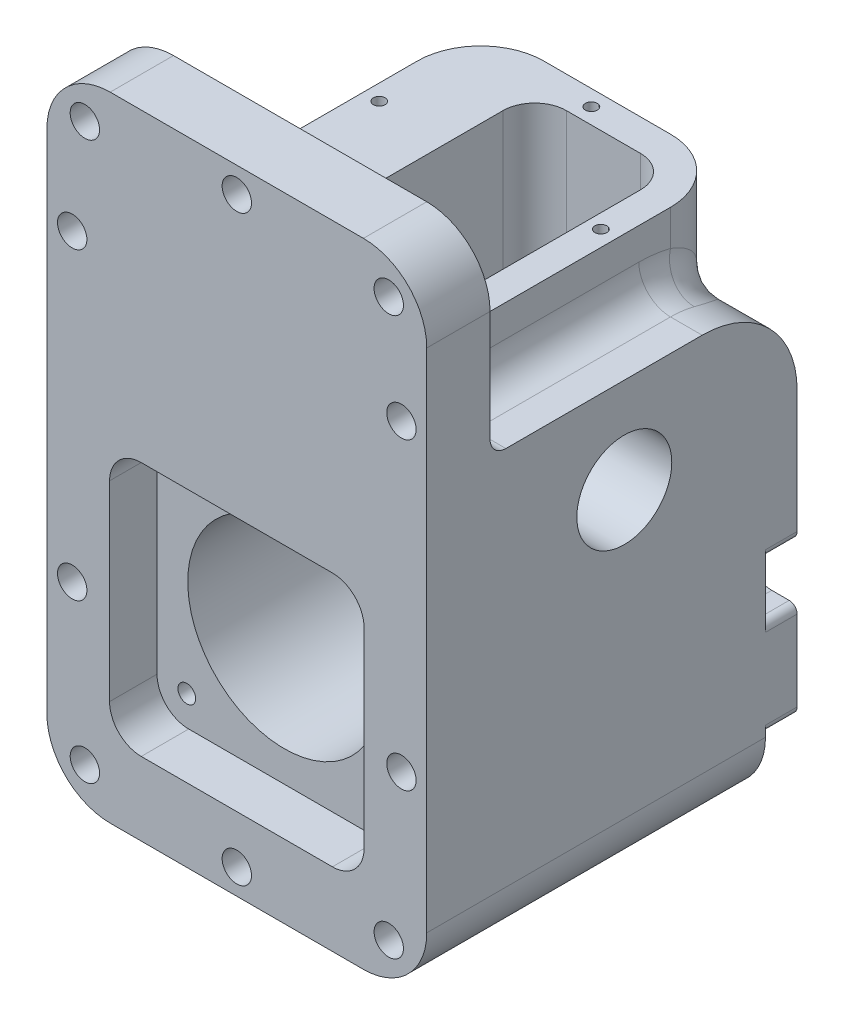
SolidWorks part; units mm, degrees
ref_plane "Front Plane" through (0, 0, 0) normal (0, 0, 1) x (1, 0, 0)
ref_plane "Top Plane" through (0, 0, 0) normal (0, 1, 0) x (1, 0, 0)
ref_plane "Right Plane" through (0, 0, 0) normal (1, 0, 0) x (0, 0, -1)
sketch "Sketch2" plane through (0, 0, 0) normal (0, 0, 1) x (1, 0, 0)
  line L1 (-19.05, -31.75) -> (19.05, -31.75)
  line L2 (-19.05, -31.75) -> (-19.05, 31.75)
  line L3 (-19.05, 31.75) -> (19.05, 31.75)
  line L4 (19.05, -31.75) -> (19.05, 31.75)
  line L5 (-19.05, -31.75) -> (19.05, 31.75) construction
  line L6 (-19.05, 31.75) -> (19.05, -31.75) construction
  point P0 (0, 0)
  dimension "D1" = 63.5
  dimension "D2" = 38.1
extrude "Boss-Extrude1" add sketch "Sketch2" along normal blind 6.35
fillet "Fillet1" radius 6.35 4 edges at (-19.05, -31.75, 3.175) (19.05, -31.75, 3.175) (-19.05, 31.75, 3.175) (19.05, 31.75, 3.175)
hole_wizard "#4 Clearance Hole1" positions "Sketch4" profile "Sketch5" hole size "#4" standard "Ansi Inch" end condition through all
sketch "Sketch4" plane through (0, 0, 6.35) normal (0, 0, 1) x (1, 0, 0)
  line L0 (12.7, 31.75) -> (-12.7, 31.75) construction
  line L1 (-12.7, -31.75) -> (12.7, -31.75) construction
  line L2 (-17.1901, -29.8901) -> (0, -12.7) construction
  line L3 (0, -12.7) -> (17.1901, -29.8901) construction
  line L5 (-17.1901, 29.8901) -> (0, 12.7) construction
  line L6 (0, 12.7) -> (17.1901, 29.8901) construction
  line L8 (-19.05, 25.4) -> (-19.05, -25.4) construction
  line L9 (19.05, -25.4) -> (19.05, 25.4) construction
  arc A0 (-19.05, -25.4) -> (-12.7, -31.75) centre (-12.7, -25.4) ccw construction
  arc A1 (12.7, -31.75) -> (19.05, -25.4) centre (12.7, -25.4) ccw construction
  arc A2 (-12.7, 31.75) -> (-19.05, 25.4) centre (-12.7, 25.4) ccw construction
  arc A3 (19.05, 25.4) -> (12.7, 31.75) centre (12.7, 25.4) ccw construction
  point P0 (0, 29.21)
  point P1 (-15.24, 27.94)
  point P3 (15.24, 27.94)
  point P5 (-15.24, -27.94)
  point P7 (15.24, -27.94)
  point P9 (-16.51, 17.78)
  point P11 (-16.51, -12.7)
  point P13 (16.51, 17.78)
  point P15 (16.51, -12.7)
  point P17 (0, -29.21)
  dimension "D1" = 2.54
  dimension "D2" = 2.54
  dimension "D3" = 15.24
  dimension "D4" = 15.24
  dimension "D5" = 2.54
  dimension "D6" = 2.54
  dimension "D7" = 17.78
  dimension "D8" = 30.48
  dimension "D9" = 30.48
  dimension "D10" = 17.78
sketch "Sketch5" plane through (0, 29.21, 6.35) normal (1, 0, 0) x (0, -1, 0)
  line L0 (0, 0) -> (0, 6.35)
  line L1 (0, 6.35) -> (1.4732, 6.35)
  line L2 (1.4732, 6.35) -> (1.4732, 0)
  line L5 (1.4732, 0) -> (0, 0)
  line L11 (0, -6.35) -> (0, 107.95) construction
  dimension "Thru Hole Dia." = 2.9464
  dimension "Thru Hole Depth" = 6.35
sketch "Sketch6" plane through (0, 0, 0) normal (0, 0, -1) x (-1, 0, 0)
  line L1 (-12.7, -25.4) -> (12.7, -25.4)
  line L2 (-12.7, -25.4) -> (-12.7, 25.4)
  line L3 (-12.7, 25.4) -> (12.7, 25.4)
  line L4 (12.7, -25.4) -> (12.7, 25.4)
  line L5 (-12.7, -25.4) -> (12.7, 25.4) construction
  line L6 (-12.7, 25.4) -> (12.7, -25.4) construction
  point P0 (0, 0)
  dimension "D1" = 50.8
  dimension "D2" = 25.4
extrude "Boss-Extrude2" add sketch "Sketch6" along normal blind 35.56
sketch "Sketch7" plane through (0, 0, -35.56) normal (0, 0, -1) x (-1, 0, 0)
  line L0 (0, -25.4) -> (0, 25.4) construction
  line L1 (-12.7, -25.4) -> (12.7, -25.4) construction
  line L2 (12.7, 25.4) -> (-12.7, 25.4) construction
  line L3 (-12.7, 0) -> (12.7, 0) construction
  line L4 (-12.7, 25.4) -> (-12.7, -25.4) construction
  line L5 (12.7, -25.4) -> (12.7, 25.4) construction
  line L6 (-12.7, 3.175) -> (12.7, 3.175) construction
  line L7 (-12.7, 25.4) -> (-12.7, -25.4) construction
  line L8 (12.7, -25.4) -> (12.7, 25.4) construction
  circle A0 centre (0, -11.6332) radius 3.9688
  circle A1 centre (0, -11.6332) radius 11 construction
  dimension "D1" = 7.9375
  dimension "D4" = 22
  dimension "D2" = 3.175
  dimension "D3" = 14.8082
extrude "Cut-Extrude1" cut sketch "Sketch7" against normal through all
sketch "Sketch9" plane through (12.7, 0, 0) normal (1, 0, 0) x (0, 0, -1)
  line L0 (0, 0) -> (35.56, 0) construction
  line L1 (35.56, 25.4) -> (35.56, -25.4) construction
  line L2 (-6.35, -25.4) -> (-6.35, 25.4) construction
  circle A0 centre (13.462, 3.175) radius 4.7625
  dimension "D2" = 9.525
  dimension "D1" = 3.175
  dimension "D3" = 19.812
extrude "Cut-Extrude3" cut sketch "Sketch9" against normal through all
sketch "Sketch8" plane through (0, 0, 6.35) normal (0, 0, 1) x (1, 0, 0)
  circle A0 centre (0, -11.6332) radius 9.6837
  dimension "D1" = 19.3675
extrude "Cut-Extrude2" cut sketch "Sketch8" against normal offset from surface (38.735 mm away) 3.175 up to face at (-3.9688, -11.6332, -35.56)
sketch "Sketch11" plane through (0, 0, -32.385) normal (0, 0, 1) x (1, 0, 0)
  circle A0 centre (0, -11.6332) radius 9.6837
  circle A1 centre (0, -11.6332) radius 3.9688 construction
  circle A2 centre (0, -11.6332) radius 3.9688
  circle A3 centre (0, -11.6332) radius 9.6837 construction
extrude "Boss-Extrude3" add sketch "Sketch11" along normal offset from surface (7.9375 mm away) 11.1125 up to face at (-3.9688, -11.6332, -35.56)
sketch "Sketch10" plane through (0, 25.4, 0) normal (0, 1, 0) x (1, 0, 0)
  line L3 (0, 35.56) -> (0, 0) construction
  line L4 (-4.0957, 0) -> (9.6838, 0)
  line L5 (-4.0957, 0) -> (-4.0958, 27.6225)
  line L6 (-4.0958, 27.6225) -> (9.6837, 27.6225)
  line L7 (9.6838, 0) -> (9.6837, 27.6225)
  line L9 (-12.7, 0) -> (12.7, 0) construction
  line L10 (-12.7, 35.56) -> (12.7, 35.56) construction
  point P4 (0, 17.78)
  point P6 (2.794, 17.78)
  dimension "D1" = 13.7795
  dimension "D2" = 27.6225
  dimension "D3" = 4.0957
extrude "Cut-Extrude4" cut sketch "Sketch10" against normal blind 30.48
fillet "Fillet4" [suppressed] radius 3.175
fillet "Fillet5" radius 3.175 4 edges at (-4.0957, 11.2709, 0) (-4.0958, 10.16, -27.6225) (9.6838, 10.16, 0) (9.6837, 10.16, -27.6225)
sketch "Sketch13" plane through (0, 0, 6.35) normal (0, 0, 1) x (1, 0, 0)
  line L0 (0, -1.9495) -> (9.6837, -1.9495)
  line L1 (9.6837, -11.6332) -> (9.6837, -1.9495)
  arc A0 (-4.0958, -2.8582) -> (7.1296, -5.08) centre (0, -11.6332) ccw construction
  arc A1 (9.6837, -11.6332) -> (0, -1.9495) centre (0, -11.6332) ccw
extrude "Cut-Extrude5" cut sketch "Sketch13" against normal up to surface (30.7975 mm away) up to face at (-1.4863, -10.0606, -24.4475)
fillet "Fillet6" radius 3.175 1 edges at (9.6838, -1.9495, 1.5875)
sketch "Sketch14" plane through (12.7, 0, 0) normal (1, 0, 0) x (0, 0, -1)
  line L0 (35.56, -25.4) -> (0, -25.4) construction
  line L1 (35.56, 25.4) -> (30.7975, 25.4)
  line L2 (35.56, 25.4) -> (35.56, -25.4)
  line L3 (35.56, -25.4) -> (30.7975, -25.4)
  line L4 (30.7975, 25.4) -> (30.7975, -25.4)
  dimension "D1" = 4.7625
extrude "Cut-Extrude6" cut sketch "Sketch14" against normal up to next
sketch "Sketch15" plane through (0, 0, -30.7975) normal (0, 0, -1) x (-1, 0, 0)
  line L0 (12.7, -25.4) -> (12.7, 25.4) construction
  line L1 (-12.7, 25.4) -> (12.7, 25.4)
  line L2 (-12.7, 25.4) -> (-12.7, 19.05)
  line L3 (-12.7, 19.05) -> (12.7, 19.05)
  line L4 (12.7, 25.4) -> (12.7, 19.05)
  dimension "D1" = 6.35
extrude "Cut-Extrude7" cut sketch "Sketch15" against normal up to surface (30.7975 mm away) up to face at (1.2417, 4.991, 0)
fillet "Fillet8" [suppressed] radius 6.35
hole_wizard "#0-80 Tapped Hole1" positions "Sketch21" profile "Sketch22" tap size "#0-80" standard "Ansi Inch"
sketch "Sketch21" plane through (0, 19.05, 0) normal (0, 1, 0) x (-1, 0, 0)
  line L3 (12.7, 0) -> (0.9207, 0) construction
  line L5 (12.7, 0) -> (12.7, -30.7975) construction
  line L6 (0, -30.7975) -> (0, -27.6225) construction
  line L7 (-12.7, -30.7975) -> (12.7, -30.7975) construction
  line L8 (-6.5087, -27.6225) -> (0.9208, -27.6225) construction
  line L10 (-12.7, 0) -> (-12.7, -30.7975) construction
  point P0 (-11.1125, -19.05)
  point P6 (11.1125, -19.05)
  point P10 (0, -29.21)
  point P14 (-11.1125, -6.35)
  point P16 (11.1125, -6.35)
  dimension "D1" = 6.35
  dimension "D2" = 12.7
  dimension "D3" = 1.5875
  dimension "D4" = 1.5875
  dimension "D5" = 1.5875
sketch "Sketch22" plane through (11.1125, 19.05, -19.05) normal (1, 0, 0) x (0, 0, 1)
  line L0 (0, 0) -> (0, 4.4219)
  line L1 (0, 4.4219) -> (0.5956, 4.064)
  line L2 (0.5956, 4.064) -> (0.5956, 0)
  line L5 (0.5956, 0) -> (0, 0)
  line L10 (0, 4.4219) -> (-0.5956, 4.064) construction
  line L11 (0, -6.35) -> (0, 107.95) construction
  dimension "Tap Drill Dia." = 1.1913
  dimension "Tap Drill Depth" = 4.064
  dimension "Drill Angle" = 118
cosmetic thread "Hole Thread1" parameters "D1"=3.048, "D2"=1.524
cosmetic thread "Hole Thread2" parameters "D1"=3.048, "D2"=1.524
cosmetic thread "Hole Thread3" parameters "D1"=3.048, "D2"=1.524
cosmetic thread "Hole Thread4" parameters "D1"=3.048, "D2"=1.524
cosmetic thread "Hole Thread5" parameters "D1"=3.048, "D2"=1.524
sketch "Sketch23" plane through (0, 0, 6.35) normal (0, 0, 1) x (1, 0, 0)
  line L1 (-12.7635, -24.3967) -> (12.7635, -24.3967)
  line L2 (-12.7635, -24.3967) -> (-12.7635, 1.1303)
  line L3 (-12.7635, 1.1303) -> (12.7635, 1.1303)
  line L4 (12.7635, -24.3967) -> (12.7635, 1.1303)
  line L5 (-12.7635, -24.3967) -> (12.7635, 1.1303) construction
  line L6 (-12.7635, 1.1303) -> (12.7635, -24.3967) construction
  point P0 (0, -11.6332)
  dimension "D1" = 25.527
  dimension "D2" = 25.527
extrude "Cut-Extrude11" cut sketch "Sketch23" against normal blind 4.7625
fillet "Fillet9" radius 3.175 4 edges at (12.7635, 1.1303, 3.9688) (12.7635, -24.3967, 3.9688) (-12.7635, 1.1303, 3.9688) (-12.7635, -24.3967, 3.9688)
sketch "Sketch24" plane through (0, 0, 1.5875) normal (0, 0, 1) x (1, 0, 0)
  line L1 (-9.779, -21.4122) -> (9.779, -21.4122) construction
  line L2 (-9.779, -21.4122) -> (-9.779, -1.8542) construction
  line L3 (-9.779, -1.8542) -> (9.779, -1.8542) construction
  line L4 (9.779, -21.4122) -> (9.779, -1.8542) construction
  line L5 (-9.779, -21.4122) -> (9.779, -1.8542) construction
  line L6 (-9.779, -1.8542) -> (9.779, -21.4122) construction
  point P0 (0, -11.6332)
  dimension "D1" = 19.558
  dimension "D2" = 19.558
hole_wizard "#2-56 Tapped Hole1" positions "Sketch26" profile "Sketch25" tap size "#2-56" standard "Ansi Inch"
sketch "Sketch26" plane through (0, 0, 1.5875) normal (0, 0, 1) x (1, 0, 0)
  point P0 (-9.779, -1.8542)
  point P4 (-9.779, -21.4122)
  point P7 (9.779, -21.4122)
sketch "Sketch25" plane through (-9.779, -1.8542, 1.5875) normal (1, 0, 0) x (0, -1, 0)
  line L0 (0, 0) -> (0, 6.1222)
  line L1 (0, 6.1222) -> (0.889, 5.588)
  line L2 (0.889, 5.588) -> (0.889, 0)
  line L5 (0.889, 0) -> (0, 0)
  line L10 (0, 6.1222) -> (-0.889, 5.588) construction
  line L11 (0, -6.35) -> (0, 107.95) construction
  dimension "Tap Drill Dia." = 1.778
  dimension "Tap Drill Depth" = 5.588
  dimension "Drill Angle" = 118
cosmetic thread "Hole Thread6" parameters "D1"=4.318, "D2"=2.1844
cosmetic thread "Hole Thread7" parameters "D1"=4.318, "D2"=2.1844
cosmetic thread "Hole Thread9" parameters "D1"=4.318, "D2"=2.1844
sketch "Sketch27" plane through (12.7, 0, 0) normal (1, 0, 0) x (0, 0, -1)
  line L0 (30.7975, 12.7) -> (0, 12.7)
  line L1 (0, -25.4) -> (0, 25.4) construction
  line L2 (30.7975, -6.35) -> (0, -6.35)
  line L3 (0, -6.35) -> (0, 12.7)
  line L4 (30.7975, 19.05) -> (30.7975, -25.4) construction
  line L5 (30.7975, 12.7) -> (30.7975, -6.35)
  circle A1 centre (13.462, 3.175) radius 4.7625 construction
  circle A2 centre (13.462, 3.175) radius 4.7625
  dimension "D1" = 19.05
  dimension "D2" = 9.525
extrude "Boss-Extrude4" add sketch "Sketch27" along normal blind 6.35
mirror "Mirror1" about plane through (0, 0, 0) normal (1, 0, 0) of "Boss-Extrude4"
ref_axis "Axis2" through (9.6837, 3.175, -13.462) along (1, 0, 0)
ref_plane "Plane1" through (0, 0, -13.462) normal (0, 0, -1) x (-1, 0, 0)
sketch "Sketch30" plane through (0, 0, 0) normal (0, 0, -1) x (-1, 0, 0)
  line L0 (-19.05, -25.4) -> (-19.05, -6.35) construction
  line L1 (-19.05, -25.4) -> (-19.05, -6.35)
  line L6 (19.05, -6.35) -> (12.7, -6.35)
  line L7 (19.05, -6.35) -> (12.7, -6.35)
  line L12 (12.7, -6.35) -> (12.7, -25.4)
  line L13 (12.7, -6.35) -> (12.7, -25.4)
  line L14 (12.7, -25.4) -> (-12.7, -25.4)
  line L15 (-19.05, -6.35) -> (-19.05, -25.4)
  line L16 (-12.7, -31.75) -> (12.7, -31.75)
  line L17 (19.05, -25.4) -> (19.05, -6.35)
  line L18 (12.7, -25.4) -> (-12.7, -25.4)
  line L19 (-12.7, -25.4) -> (-12.7, -6.35)
  line L20 (-12.7, -25.4) -> (-12.7, -6.35)
  line L21 (-12.7, -6.35) -> (-19.05, -6.35)
  line L22 (-12.7, -6.35) -> (-19.05, -6.35)
  line L23 (-19.05, -6.35) -> (-19.05, -25.4)
  line L24 (-12.7, -31.75) -> (12.7, -31.75)
  line L25 (19.05, -25.4) -> (19.05, -6.35)
  arc A2 (-19.05, -25.4) -> (-12.7, -31.75) centre (-12.7, -25.4) ccw
  arc A3 (12.7, -31.75) -> (19.05, -25.4) centre (12.7, -25.4) ccw
  arc A4 (-19.05, -25.4) -> (-12.7, -31.75) centre (-12.7, -25.4) ccw
  arc A5 (12.7, -31.75) -> (19.05, -25.4) centre (12.7, -25.4) ccw
  line M11 (19.05, -6.35) -> (12.7, -6.35)
  line M12 (12.7, -6.35) -> (12.7, -25.4)
  line M13 (12.7, -25.4) -> (-12.7, -25.4)
  line M14 (-12.7, -25.4) -> (-12.7, -6.35)
  line M15 (-12.7, -6.35) -> (-19.05, -6.35)
  line M16 (-19.05, -6.35) -> (-19.05, -25.4)
  arc M17 (-19.05, -25.4) -> (-12.7, -31.75) centre (-12.7, -25.4) ccw
  line M18 (-12.7, -31.75) -> (12.7, -31.75)
  arc M19 (12.7, -31.75) -> (19.05, -25.4) centre (12.7, -25.4) ccw
  line M20 (19.05, -25.4) -> (19.05, -6.35)
  circle M21 centre (15.24, -27.94) radius 1.4732
  circle M22 centre (-15.24, -27.94) radius 1.4732
  circle M23 centre (16.51, -12.7) radius 1.4732
  circle M24 centre (-16.51, -12.7) radius 1.4732
  circle M25 centre (0, -29.21) radius 1.4732
  dimension "D1" = 0
extrude "Boss-Extrude5" add sketch "Sketch30" along normal up to surface (30.7975 mm away) contours M20 M11 M12 M13 M14 M15 M16 M17 M18 M19 M21 M23 M25 M24 M22 region at (18.5921, -15.875, 0) up to face at (0, 1.0583, -30.7975)
fillet "Fillet10" radius 9.525 2 edges at (-15.875, 12.7, -30.7975) (15.875, 12.7, -30.7975)
sketch "Sketch33" plane through (0, 0, -30.7975) normal (0, 0, -1) x (-1, 0, 0)
  line L0 (-16.51, -9.906) -> (-19.05, -9.906)
  line L1 (-19.05, -25.4) -> (-19.05, 3.175) construction
  line L2 (16.51, -9.906) -> (19.05, -9.906)
  line L3 (-16.51, -15.494) -> (-19.05, -15.494)
  line L4 (-19.05, -15.494) -> (-19.05, -9.906)
  line L5 (-19.05, -15.494) -> (-19.05, -9.906)
  line L6 (-12.446, -31.75) -> (-12.7, -31.75)
  line L7 (19.05, -9.906) -> (19.05, -15.494)
  line L8 (19.05, -25.4) -> (19.05, 3.175) construction
  line L9 (19.05, -15.494) -> (16.51, -15.494)
  line L10 (12.446, -27.94) -> (12.446, -31.75)
  line L11 (12.7, -31.75) -> (-12.7, -31.75) construction
  line L12 (15.24, -25.146) -> (19.05, -25.146)
  line L13 (19.05, -25.4) -> (19.05, 3.175)
  line L14 (12.7, -31.75) -> (12.446, -31.75)
  line L15 (-2.794, -29.21) -> (-2.794, -31.75)
  line L16 (2.794, -29.21) -> (2.794, -31.75)
  line L17 (-19.05, -25.4) -> (-19.05, -25.146)
  line L18 (-15.24, -25.146) -> (-19.05, -25.146)
  line L19 (-12.446, -27.94) -> (-12.446, -31.75)
  line L20 (2.794, -31.75) -> (-2.794, -31.75)
  arc A0 (-16.51, -15.494) -> (-16.51, -9.906) centre (-16.51, -12.7) ccw
  arc A1 (-17.5908, -29.45) -> (-16.75, -30.2908) centre (-15.24, -27.94) ccw
  arc A2 (2.794, -29.21) -> (-2.794, -29.21) centre (0, -29.21) ccw
  arc A3 (16.75, -30.2908) -> (17.5908, -29.45) centre (15.24, -27.94) ccw
  arc A4 (16.51, -9.906) -> (16.51, -15.494) centre (16.51, -12.7) ccw
  arc A5 (12.7, -31.75) -> (19.05, -25.4) centre (12.7, -25.4) ccw construction
  arc A6 (12.7, -31.75) -> (19.05, -25.4) centre (12.7, -25.4) ccw
  arc A7 (-19.05, -25.4) -> (-12.7, -31.75) centre (-12.7, -25.4) ccw construction
  arc A8 (-19.05, -25.4) -> (-12.7, -31.75) centre (-12.7, -25.4) ccw
  arc A9 (-12.446, -27.94) -> (-15.24, -25.146) centre (-15.24, -27.94) ccw
  arc A10 (15.24, -25.146) -> (12.446, -27.94) centre (15.24, -27.94) ccw
  line M1 (19.05, -25.4) -> (19.05, 3.175)
  line M7 (-19.05, 3.175) -> (-19.05, -25.4)
  arc M8 (-19.05, -25.4) -> (-12.7, -31.75) centre (-12.7, -25.4) ccw
  line M9 (-12.7, -31.75) -> (12.7, -31.75)
  arc M10 (12.7, -31.75) -> (19.05, -25.4) centre (12.7, -25.4) ccw
  circle M12 centre (-16.51, -12.7) radius 1.4732
  circle M13 centre (16.51, -12.7) radius 1.4732
  circle M14 centre (15.24, -27.94) radius 1.4732
  circle M15 centre (0, -29.21) radius 1.4732
  circle M16 centre (-15.24, -27.94) radius 1.4732
  dimension "D1" = 5.588
  dimension "D2" = 2.794
  dimension "D3" = 2.794
  dimension "D4" = 2.794
extrude "Cut-Extrude12" cut sketch "Sketch33" against normal blind 3.175 contours L3 A0 L0 M7 M12 | L19 A9 L18 M7 M8 M9 M16 | L16 A2 L15 M9 M15 | L12 A10 L10 M9 M10 M1 M14 | L2 A4 L9 M1 M13 | L7 L9 A4 L2 region at (13.7933, -12.7, -30.7975) region at (-17.78, -15.4167, -30.7975) region at (-12.5394, -29.845, -30.7975) region at (2.7167, -30.48, -30.7975) region at (17.145, -25.2394, -30.7975)
fillet "Fillet11" radius 0.7937 10 edges at (-19.05, -9.906, -29.21) (-19.05, -15.494, -29.21) (-19.05, -25.146, -29.21) (-12.446, -31.75, -29.21) (-2.794, -31.75, -29.21) (2.794, -31.75, -29.21) (12.446, -31.75, -29.21) (19.05, -25.146, -29.21) (19.05, -15.494, -29.21) (19.05, -9.906, -29.21)
fillet "Fillet12" radius 6.35 2 edges at (-12.7, 11.1125, -30.7975) (12.7, 11.1125, -30.7975)
fillet "Fillet13" radius 3.175 6 edges at (-12.7, 12.7, -10.6363) (-12.7, 12.5628, -22.8832) (12.7, 12.7, -10.6363) (12.7, 12.5628, -22.8832) (-11.3316, 9.5101, -28.3853) (11.3316, 9.5101, -28.3853)
fillet "Fillet14" radius 1.5875 6 edges at (-12.7, 17.4625, 0) (-17.4625, 12.7, 0) (17.4625, 12.7, 0) (12.7, 17.4625, 0) (-13.6299, 13.6299, 0) (13.6299, 13.6299, 0)
hole_wizard "#8-32 Tapped Hole1" positions "Sketch35" profile "Sketch34" tap size "#8-32" standard "Ansi Inch"
sketch "Sketch35" plane through (0, 0, -30.7975) normal (0, 0, -1) x (-1, 0, 0)
  line L0 (-3.5878, -31.75) -> (-11.6523, -31.75) construction
  point P0 (-14.2875, -5.08)
  point P2 (14.2875, -5.08)
  point P4 (-8.255, -24.13)
  point P6 (8.255, -24.13)
  dimension "D1" = 7.62
  dimension "D2" = 8.255
  dimension "D3" = 16.51
  dimension "D4" = 19.05
  dimension "D5" = 28.575
  dimension "D6" = 14.2875
sketch "Sketch34" plane through (14.2875, -5.08, -30.7975) normal (1, 0, 0) x (0, 1, 0)
  line L0 (0, 0) -> (0, 11.7058)
  line L1 (0, 11.7058) -> (1.7272, 10.668)
  line L2 (1.7272, 10.668) -> (1.7272, 0)
  line L5 (1.7272, 0) -> (0, 0)
  line L10 (0, 11.7058) -> (-1.7272, 10.668) construction
  line L11 (0, -6.35) -> (0, 107.95) construction
  dimension "Tap Drill Dia." = 3.4544
  dimension "Tap Drill Depth" = 10.668
  dimension "Drill Angle" = 118
cosmetic thread "Hole Thread10" parameters "D1"=8.382, "D2"=4.1656
cosmetic thread "Hole Thread11" parameters "D1"=8.382, "D2"=4.1656
cosmetic thread "Hole Thread12" parameters "D1"=8.382, "D2"=4.1656
cosmetic thread "Hole Thread13" parameters "D1"=8.382, "D2"=4.1656
